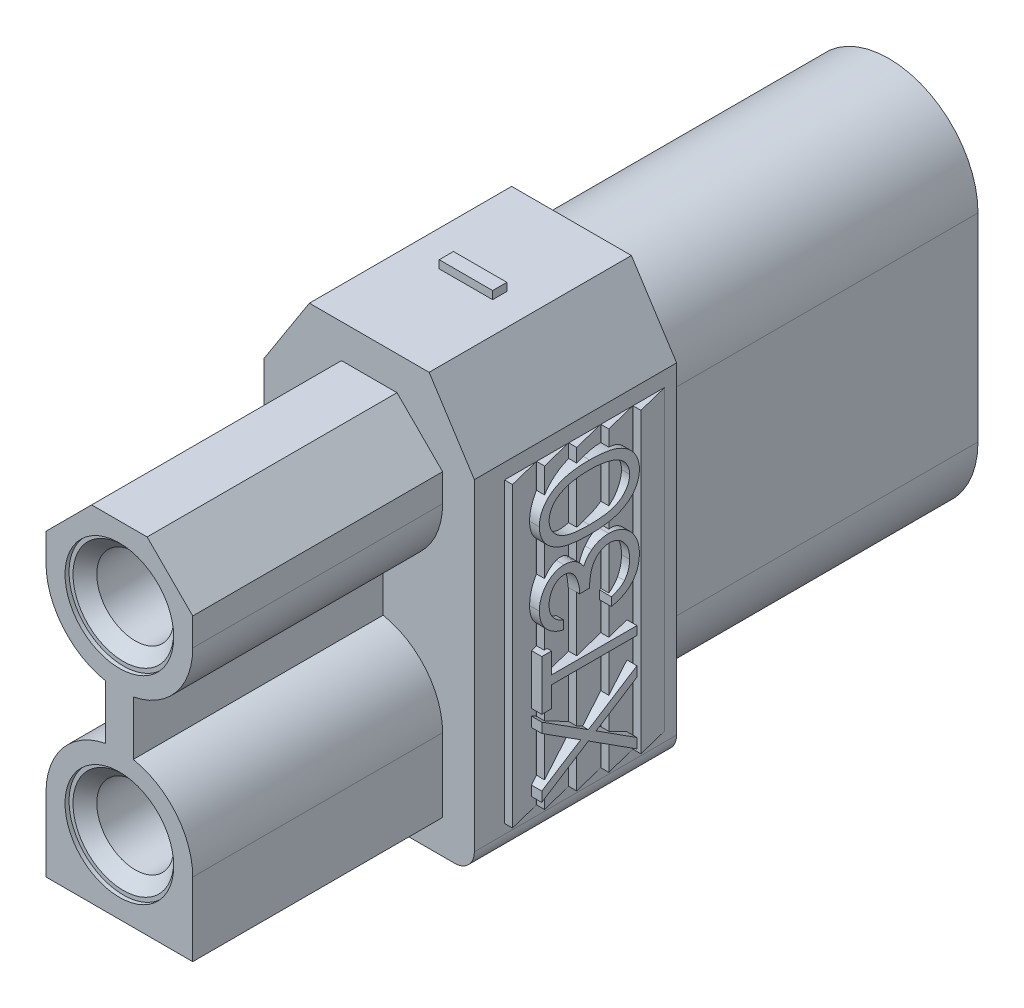
SolidWorks part; units mm, degrees
ref_plane "Front Plane" through (0, 0, 0) normal (0, 0, 1) x (1, 0, 0)
ref_plane "Top Plane" through (0, 0, 0) normal (0, 1, 0) x (1, 0, 0)
ref_plane "Right Plane" through (0, 0, 0) normal (1, 0, 0) x (0, 0, -1)
sketch "Sketch3" plane through (0, 0, 0) normal (0, 0, 1) x (1, 0, 0)
  line L0 (0, 1.0104) -> (0, 9.9104) construction
  line L1 (0, 5.4604) -> (-1.9, 5.4604) construction
  line L2 (0, 5.4604) -> (1.9, 5.4604) construction
  line L3 (0, 9.9104) -> (-1.1, 9.9104) construction
  line L4 (-1.1, 9.9104) -> (-1.1, 8.5104) construction
  line L5 (1.9, 1.0104) -> (-1.9, 1.0104)
  line L6 (-1.9, 1.0104) -> (-1.9, 8.6659)
  line L7 (-1.9, 8.6659) -> (-1.1, 9.9104)
  line L8 (-1.1, 9.9104) -> (1.1, 9.9104)
  line L9 (1.9, 1.0104) -> (1.9, 8.6659)
  line L10 (1.9, 8.6659) -> (1.1, 9.9104)
  line L11 (2.15, 0.2604) -> (-2.15, 0.2604)
  line L12 (-2.65, 0.7604) -> (-2.65, 8.8862)
  line L13 (-2.65, 8.8862) -> (-1.5095, 10.6604)
  line L14 (-1.5095, 10.6604) -> (1.5095, 10.6604)
  line L15 (2.65, 8.8862) -> (1.5095, 10.6604)
  line L16 (2.65, 0.7604) -> (2.65, 8.8862)
  line L17 (2.65, 0.2604) -> (-2.65, 0.2604) construction
  line L18 (2.65, 0.2604) -> (2.65, 8.8862) construction
  line L19 (-2.65, 0.2604) -> (-2.65, 8.8862) construction
  arc A0 (2.15, 0.2604) -> (2.65, 0.7604) centre (2.15, 0.7604) ccw
  arc A1 (-2.15, 0.2604) -> (-2.65, 0.7604) centre (-2.15, 0.7604) cw
  point P22 (2.65, 0.2604)
  dimension "D9" = 0.5
  dimension "D1" = 8.9
  dimension "D2" = 1.9
  dimension "D3" = 1.9
  dimension "D4" = 1.1
  dimension "D5" = 1.4
  dimension "D8" = 10.4
  dimension "D6" = 0.75
extrude "Boss-Extrude2" add sketch "Sketch3" along normal blind 5.1
sketch "Sketch4" plane through (0, 0, 0) normal (0, 0, 1) x (1, 0, 0)
  line L6 (-1.5, 10.0104) -> (1.4, 10.0104)
  line L7 (-2, 9.5104) -> (-2, 1.0104)
  line L8 (-2, 1.0104) -> (1.9, 1.0104)
  line L9 (1.9, 9.5104) -> (1.9, 1.0104)
  arc A0 (1.4, 10.0104) -> (1.9, 9.5104) centre (1.4, 9.5104) cw
  arc A1 (-1.5, 10.0104) -> (-2, 9.5104) centre (-1.5, 9.5104) ccw
  dimension "D1" = 0.5
extrude "Boss-Extrude3" add sketch "Sketch4" along normal up to surface (5.1 mm away) from offset 1.45 up to face at (0, 5.1159, 5.1)
sketch "Sketch6" plane through (0, 0, 0) normal (0, 1, 0) x (1, 0, 0)
  line L0 (2.65, -0.3) -> (2.65, -1.1)
  line L1 (2.65, -5.1) -> (2.65, 0) construction
  line L2 (2.65, -1.1) -> (2.85, -1.1)
  line L3 (2.65, 0) -> (1.5095, 0) construction
  line L4 (0, 0) -> (0, -2.7855) construction
  line L5 (2.85, -1.1) -> (2.65, -0.3)
  line L6 (2.65, -1.11) -> (2.65, -1.91)
  line L7 (2.65, -1.91) -> (2.85, -1.91)
  line L8 (2.85, -1.91) -> (2.65, -1.11)
  line L9 (2.65, -1.92) -> (2.65, -2.72)
  line L10 (2.65, -2.72) -> (2.85, -2.72)
  line L11 (2.85, -2.72) -> (2.65, -1.92)
  line L12 (2.65, -2.73) -> (2.65, -3.53)
  line L13 (2.65, -3.53) -> (2.85, -3.53)
  line L14 (2.85, -3.53) -> (2.65, -2.73)
  line L15 (2.65, -3.54) -> (2.65, -4.34)
  line L16 (2.65, -4.34) -> (2.85, -4.34)
  line L17 (2.85, -4.34) -> (2.65, -3.54)
  line L18 (-2.85, -4.34) -> (-2.65, -3.54)
  line L19 (-2.65, -4.34) -> (-2.85, -4.34)
  line L20 (-2.65, -3.54) -> (-2.65, -4.34)
  line L21 (-2.85, -3.53) -> (-2.65, -2.73)
  line L22 (-2.65, -3.53) -> (-2.85, -3.53)
  line L23 (-2.65, -2.73) -> (-2.65, -3.53)
  line L24 (-2.85, -2.72) -> (-2.65, -1.92)
  line L25 (-2.65, -2.72) -> (-2.85, -2.72)
  line L26 (-2.65, -1.92) -> (-2.65, -2.72)
  line L27 (-2.85, -1.91) -> (-2.65, -1.11)
  line L28 (-2.65, -1.91) -> (-2.85, -1.91)
  line L29 (-2.65, -1.11) -> (-2.65, -1.91)
  line L30 (-2.85, -1.1) -> (-2.65, -0.3)
  line L31 (-2.65, -1.1) -> (-2.85, -1.1)
  line L32 (-2.65, -0.3) -> (-2.65, -1.1)
  dimension "D1" = 0.3
  dimension "D2" = 0.8
  dimension "D3" = 5
  dimension "D4" = 0.2
extrude "Boss-Extrude4" add sketch "Sketch6" along normal blind 7.5 from offset 1
sketch "Sketch7" plane through (0, 0, 0) normal (0, 0, 1) x (1, 0, 0)
  line L0 (-1.9, 1.0104) -> (1.9, 1.0104) construction
  line L1 (0, 2.9604) -> (0, 7.9604) construction
  line L2 (1.1, 9.9104) -> (-1.1, 9.9104) construction
  circle A0 centre (0, 2.9604) radius 1.1
  circle A1 centre (0, 7.9604) radius 1.1
  dimension "D1" = 2.2
  dimension "D2" = 2.2
  dimension "D3" = 5
  dimension "D4" = 1.95
  dimension "D5" = 1.95
extrude "Boss-Extrude5" add sketch "Sketch7" along normal up to surface (5.1 mm away) and the other way blind 3.45 separate body up to face at (0, 5.1159, 5.1)
sketch "Sketch8" plane through (0, 0, -3.45) normal (0, 0, -1) x (-1, 0, 0)
  circle A1 centre (0, 2.9604) radius 0.65
  circle A2 centre (0, 7.9604) radius 0.65
extrude "Cut-Extrude1" cut sketch "Sketch8" against normal blind 3
sketch "Sketch9" plane through (0, 0, 0) normal (1, 0, 0) x (0, 0, -1)
  line L0 (3.45, 6.8604) -> (3.45, 9.0604) construction
  line L1 (3.45, 7.9604) -> (1.55, 7.9604)
  line L2 (3.45, 7.9604) -> (3.45, 9.0604)
  line L3 (3.45, 9.0604) -> (1.55, 9.0604)
  line L4 (1.55, 7.9604) -> (1.55, 9.0604)
  line L5 (3.45, 9.0604) -> (-5.1, 9.0604) construction
  line L6 (3.45, 1.8604) -> (3.45, 4.0604) construction
  line L7 (3.45, 2.9604) -> (1.7, 2.9604)
  line L8 (3.45, 2.9604) -> (3.45, 1.8604)
  line L9 (3.45, 1.8604) -> (1.7, 1.8604)
  line L10 (1.7, 2.9604) -> (1.7, 1.8604)
  line L11 (-5.1, 1.8604) -> (3.45, 1.8604) construction
  dimension "D1" = 1.9
extrude "Cut-Extrude2" cut sketch "Sketch9" against normal through all and the other way through all
chamfer "Chamfer1" distance 0.65 angle 45 1 edges at (-0.65, 7.9604, -0.45)
chamfer "Chamfer3" distance 0.65 angle 45 1 edges at (-0.65, 2.9604, -0.45)
sketch "Sketch10" plane through (0, 0, 5.1) normal (0, 0, 1) x (1, 0, 0)
  circle A0 centre (0, 7.9604) radius 0.97
  circle A1 centre (0, 2.9604) radius 0.97
  circle A3 centre (0, 7.9604) radius 1.37
  circle A4 centre (0, 2.9604) radius 1.37
  dimension "D1" = 0.4
extrude "Boss-Extrude6" add sketch "Sketch10" along normal blind 6.2 separate body
sketch "Sketch12" plane through (0, 0.2604, 0) normal (0, -1, 0) x (1, 0, 0)
  line L0 (0, 0) -> (0, 1) construction
  line L1 (0, 1) -> (-1.45, 1) construction
  line L2 (-1.45, 1) -> (0.8, 1) construction
  text T0 "+\r\n"
  dimension "D1" = 1
  dimension "D2" = 1.45
extrude "Boss-Extrude7" add sketch "Sketch12" along normal blind 0.2
sketch "Sketch13" plane through (0, 10.6604, 0) normal (0, 1, 0) x (-1, 0, 0)
  line L0 (0.2478, 0.1887) -> (0.2478, 1.1887) construction
  line L1 (0.2478, 1.1887) -> (-1.1522, 1.1887) construction
  line L2 (-1.1522, 1.1887) -> (1.0478, 1.1887) construction
  text T0 "-\r\n"
  dimension "D1" = 1
  dimension "D2" = 1.4
extrude "Boss-Extrude8" add sketch "Sketch13" along normal blind 0.2
sketch "Sketch14" plane through (-2.65, 0, 0) normal (-1, 0, 0) x (0, 0, 1)
  line L0 (0.3, 4.75) -> (1.3, 4.75) construction
  line L1 (0.3, 8.5) -> (0.3, 1) construction
  line L2 (1.3, 4.75) -> (1.3, 8.35) construction
  line L3 (1.3, 8.35) -> (1.3, 1.15) construction
  text T0 "XT30\r\n" font "Century Gothic" height 2.4
  dimension "D1" = 1
  dimension "D2" = 3.6
  dimension "D3" = 7.2
extrude "Boss-Extrude9" add sketch "Sketch14" along normal blind 0.3
sketch "Sketch15" plane through (2.65, 0, 0) normal (1, 0, 0) x (0, 0, -1)
  line L0 (-0.3, 4.75) -> (-1.3, 4.75) construction
  line L2 (-1.3, 4.75) -> (-1.3, 1.15) construction
  line L3 (-1.3, 1.15) -> (-1.3, 8.35) construction
  text T0 "XT30\r\n" font "Century Gothic" height 2.4
  dimension "D1" = 1
  dimension "D2" = 3.6
  dimension "D3" = 7.2
extrude "Boss-Extrude10" add sketch "Sketch15" along normal blind 0.3
chamfer "Chamfer4" distance 0.3 angle 45 1 edges at (0.97, 2.9604, 11.3)
chamfer "Chamfer5" distance 0.3 angle 45 1 edges at (0.97, 7.9604, 11.3)
sketch "Sketch17" plane through (0, 0, 5.1) normal (0, 0, 1) x (1, 0, 0)
  line L0 (0, 2.9604) -> (-1.85, 2.9604) construction
  line L1 (0, 1.1104) -> (0, 9.8104) construction
  line L2 (0, 1.1104) -> (-1.85, 1.1104)
  line L3 (-1.85, 1.1104) -> (-1.85, 2.9604)
  line L4 (0, 2.9604) -> (1.85, 2.9604) construction
  line L5 (0, 1.1104) -> (1.85, 1.1104)
  line L6 (1.85, 1.1104) -> (1.85, 2.9604)
  line L7 (0.7, 9.8104) -> (-0.7, 9.8104)
  line L8 (0, 7.9604) -> (-1.85, 7.9604) construction
  line L9 (-0.7, 9.8104) -> (-2.8213, 7.689) construction
  line L10 (-1.85, 7.9604) -> (-1.85, 8.6604)
  line L11 (-1.85, 8.6604) -> (-0.7, 9.8104)
  line L12 (1.85, 7.9604) -> (1.85, 8.6604)
  line L13 (1.85, 8.6604) -> (0.7, 9.8104)
  circle A0 centre (0, 2.9604) radius 1.37 construction
  circle A1 centre (0, 7.9604) radius 1.37 construction
  arc A2 (-1.85, 2.9604) -> (1.85, 2.9604) centre (0, 2.9604) cw
  arc A3 (-1.85, 7.9604) -> (1.85, 7.9604) centre (0, 7.9604) ccw
  circle A7 centre (0, 7.9604) radius 1.37
  circle A8 centre (0, 2.9604) radius 1.37
  dimension "D1" = 1.85
  dimension "D2" = 8.7
  dimension "D3" = 1.85
  dimension "D4" = 1.85
  dimension "D5" = 1.85
extrude "Boss-Extrude11" add sketch "Sketch17" along normal blind 6.3 separate body
sketch "Sketch18" plane through (0, 0, 5.1) normal (0, 0, 1) x (1, 0, 0)
  line L0 (0, 6.1104) -> (0, 4.8104) construction
  line L2 (-0.35, 6.3204) -> (0.35, 6.3204)
  line L3 (-0.35, 6.3204) -> (-0.35, 4.6003)
  line L4 (-0.35, 4.6003) -> (0.35, 4.6003)
  line L5 (0.35, 6.3204) -> (0.35, 4.6003)
  line L6 (-0.35, 6.3204) -> (0.35, 4.6003) construction
  line L7 (-0.35, 4.6003) -> (0.35, 6.3204) construction
  arc A0 (-1.85, 7.9604) -> (1.85, 7.9604) centre (0, 7.9604) ccw construction
  arc A1 (1.85, 2.9604) -> (-1.85, 2.9604) centre (0, 2.9604) ccw construction
  point P8 (0, 5.4604)
  dimension "D1" = 0.7
extrude "Boss-Extrude12" add sketch "Sketch18" along normal up to surface (6.3 mm away) up to face at (0, 2.4979, 11.4)
sketch "Sketch19" plane through (0, 0, 0) normal (0, 0, -1) x (-1, 0, 0)
  line L0 (0, 7.9604) -> (0, 2.9604) construction
  line L1 (2.2488, 7.9604) -> (2.2488, 2.9604)
  line L2 (-2.2488, 7.9604) -> (-2.2488, 2.9604)
  arc A0 (2.2488, 7.9604) -> (-2.2488, 7.9604) centre (0, 7.9604) ccw
  arc A1 (-2.2488, 2.9604) -> (2.2488, 2.9604) centre (0, 2.9604) ccw
  point P4 (0, 5.4604)
extrude "Boss-Extrude13" add sketch "Sketch19" along normal blind 8
